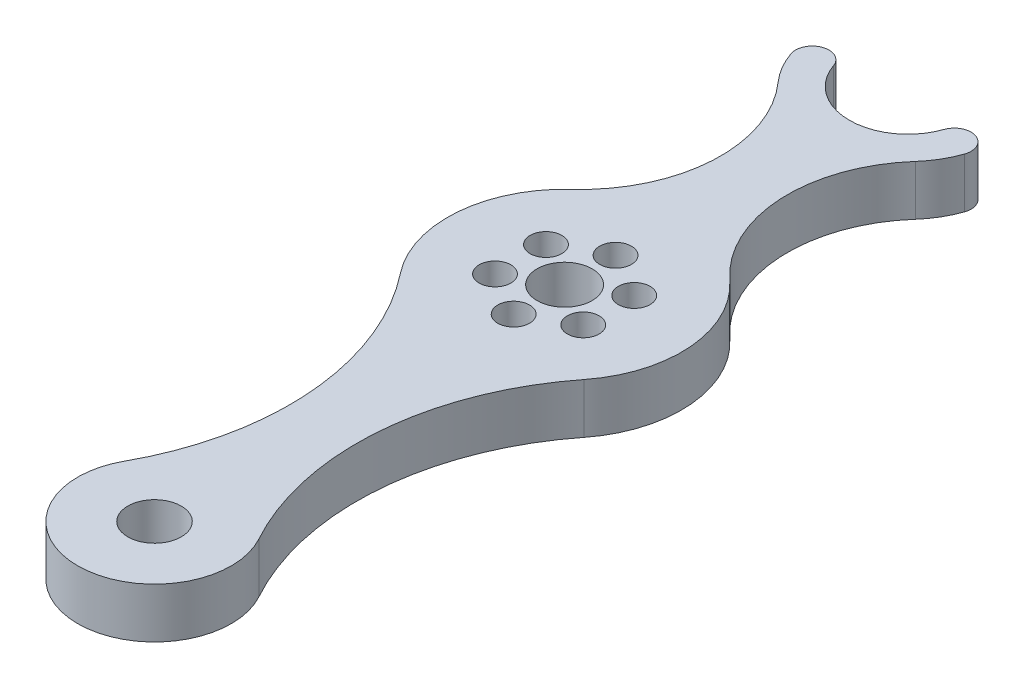
SolidWorks part; units mm, degrees
ref_plane "Front Plane" through (0, 0, 0) normal (0, 0, 1) x (1, 0, 0)
ref_plane "Top Plane" through (0, 0, 0) normal (0, 1, 0) x (1, 0, 0)
ref_plane "Right Plane" through (0, 0, 0) normal (1, 0, 0) x (0, 0, -1)
sketch "Sketch1" plane through (0, 0, 0) normal (0, 1, 0) x (1, 0, 0)
  line L0 (0, -52.0078) -> (0, -44.0078) construction
  circle A0 centre (0, -68.5564) radius 4 construction
  circle A1 centre (0, -68.5564) radius 4 construction
  arc A2 (-4.7216, -63.3885) -> (4.7216, -63.3885) centre (0, -68.5564) ccw
  circle A3 centre (0, -68.5564) radius 7 construction
  circle A4 centre (0, -48.0078) radius 4 construction
  circle A5 centre (0, -68.5564) radius 16.5485 construction
  circle A7 centre (0, -48.0078) radius 3.5 construction
  circle A14 centre (0, -68.5564) radius 1.65 construction
  circle A15 centre (0, -68.5564) radius 1.65
  arc A16 (-5.1989, -49.8026) -> (-4.1113, -51.6613) centre (0, -48.0078) ccw
  arc A17 (-4.1113, -51.6613) -> (-4.7216, -63.3885) centre (-10.3616, -57.2155) cw
  arc A18 (4.1113, -51.6613) -> (4.7216, -63.3885) centre (10.3616, -57.2155) ccw
  arc A19 (5.1989, -49.8026) -> (4.1113, -51.6613) centre (0, -48.0078) cw
  arc A20 (-3.3084, -49.1499) -> (3.3084, -49.1499) centre (0, -48.0078) ccw
  arc A21 (-5.1989, -49.8026) -> (-3.3084, -49.1499) centre (-4.2537, -49.4762) cw
  arc A22 (5.1989, -49.8026) -> (3.3084, -49.1499) centre (4.2537, -49.4762) ccw
  circle A23 centre (0, -68.5564) radius 20.5485 construction
  point P37 (-2, -57.2155)
  point P38 (2, -57.2155)
  dimension "D2" = 1
  dimension "D4" = 4
  dimension "D1" = 0.5
extrude "Boss-Extrude1" add sketch "Sketch1" along normal blind 3
sketch "Sketch2" plane through (0, 0, 0) normal (0, -1, 0) x (1, 0, 0)
  line L0 (0, 52.0078) -> (0, 44.0078) construction
  circle A0 centre (0, 93.1049) radius 1.6
  arc A2 (-4.0291, 90.8855) -> (4.0291, 90.8855) centre (0, 93.1049) cw
  arc A3 (-4.0291, 90.8855) -> (-5.5011, 72.8851) centre (-18.351, 82.9963) cw
  arc A4 (4.7216, 63.3885) -> (-4.7216, 63.3885) centre (0, 68.5564) ccw construction
  arc A5 (4.0291, 90.8855) -> (5.5011, 72.8851) centre (18.351, 82.9963) ccw
  arc A6 (-5.5011, 72.8851) -> (5.5011, 72.8851) centre (0, 68.5564) cw
  circle A7 centre (0, 68.5564) radius 24.5485 construction
  point P5 (0, 94.7049)
  point P6 (0, 97.7049)
  point P14 (-2, 82.9963)
  point P17 (2, 82.9963)
  dimension "D1" = 3.2
  dimension "D2" = 3
extrude "Boss-Extrude2" add sketch "Sketch2" against normal up to surface (3 mm away) up to face at (0, 3, 55.1247)
sketch "Sketch3" plane through (0, 3, 0) normal (0, 1, 0) x (1, 0, 0)
  circle A0 centre (0, -65.5064) radius 0.95
  circle A1 centre (0, -68.5564) radius 4 construction
  circle A2 centre (2.6414, -67.0314) radius 0.95
  circle A3 centre (2.6414, -70.0814) radius 0.95
  circle A4 centre (0, -71.6064) radius 0.95
  circle A5 centre (-2.6414, -70.0814) radius 0.95
  circle A6 centre (-2.6414, -67.0314) radius 0.95
  point P17 (0, -68.5564)
  dimension "D1" = 1.9
  dimension "D2" = 6
extrude "Cut-Extrude1" cut sketch "Sketch3" against normal through all
ref_axis "Axis1" through (0, 3, 93.1049) along (0, -1, 0)
